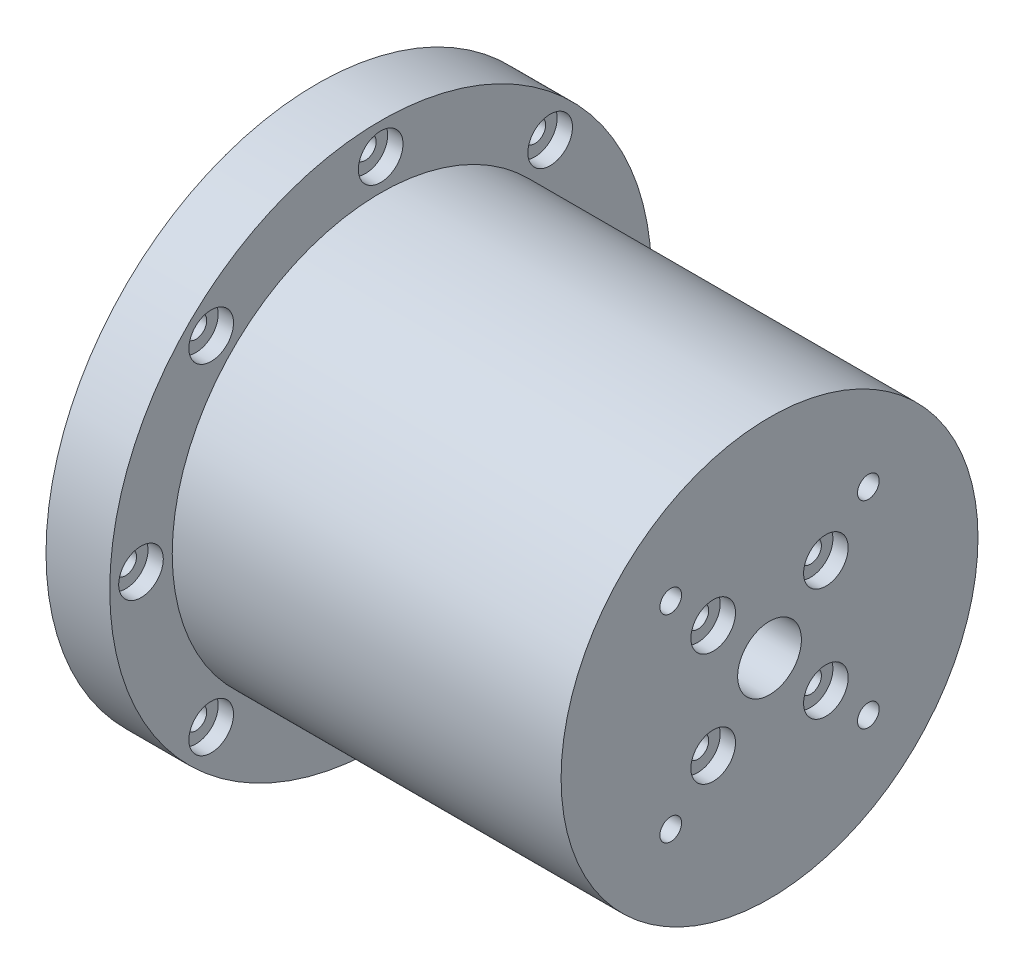
SolidWorks part; units mm, degrees
material "7075-O (SS)"
ref_plane "Front" through (0, 0, 0) normal (0, 0, 1) x (1, 0, 0)
ref_plane "Top" through (0, 0, 0) normal (0, 1, 0) x (1, 0, 0)
ref_plane "Right" through (0, 0, 0) normal (1, 0, 0) x (0, 0, -1)
sketch "Croquis1" plane through (0, 0, 0) normal (1, 0, 0) x (0, 0, -1)
  circle A0 centre (0, 0) radius 32.7
  circle A1 centre (0, 0) radius 5
  dimension "D1" = 65.4
  dimension "D2" = 10
extrude "Saliente-Extruir1" add sketch "Croquis1" along normal mid plane 8.5
hole_wizard "Refrentado para tornillo con cabeza troncocónica de M31" positions "Croquis2" profile "Croquis4" counterbore size "M3" standard "Ansi Metric" end condition up to next
sketch "Croquis2" plane through (4.25, 0, 0) normal (1, 0, 0) x (0, 0, -1)
  line L1 (-8.8388, -8.8388) -> (8.8388, -8.8388) construction
  line L2 (-8.8388, -8.8388) -> (-8.8388, 8.8388) construction
  line L3 (-8.8388, 8.8388) -> (8.8388, 8.8388) construction
  line L4 (8.8388, -8.8388) -> (8.8388, 8.8388) construction
  line L5 (-8.8388, -8.8388) -> (8.8388, 8.8388) construction
  line L6 (-8.8388, 8.8388) -> (8.8388, -8.8388) construction
  point P2 (8.8388, 8.8388)
  point P25 (-8.8388, -8.8388)
  point P26 (-8.8388, 8.8388)
  point P27 (8.8388, -8.8388)
  dimension "D1" = 25
sketch "Croquis4" plane through (4.25, 8.8388, -8.8388) normal (0, 1, 0) x (0, 0, -1)
  line L0 (0, 0) -> (0, 8.5)
  line L1 (0, 8.5) -> (1.7, 8.5)
  line L3 (1.7, 8.5) -> (1.7, 2.4)
  line L4 (1.7, 2.4) -> (3.5, 2.4)
  line L5 (3.5, 2.4) -> (3.5, 0)
  line L7 (3.5, 0) -> (0, 0)
  line L11 (0, -6.35) -> (0, 107.95) construction
  dimension "Diámetro de taladro hasta el siguiente" = 3.4
  dimension "Profundidad de taladro hasta el siguiente" = 8.5
  dimension "Diámetro de refrentado" = 7
  dimension "Profundidad de refrentado" = 2.4
sketch "Croquis5" plane through (-4.25, 0, 0) normal (-1, 0, 0) x (0, 0, 1)
  circle A0 centre (0, 0) radius 21.5
  circle A1 centre (0, 0) radius 32.7 construction
  circle A2 centre (0, 0) radius 32.7
  dimension "D1" = 43
extrude "Saliente-Extruir2" add sketch "Croquis5" along normal blind 55
hole_wizard "Taladro de margen para M31" positions "Croquis6" profile "Croquis8" hole size "M3" standard "Ansi Metric"
sketch "Croquis6" plane through (-59.25, 0, 0) normal (-1, 0, 0) x (0, 0, 1)
  line L1 (-17.075, -17.075) -> (17.075, -17.075) construction
  line L2 (-17.075, -17.075) -> (-17.075, 17.075) construction
  line L3 (-17.075, 17.075) -> (17.075, 17.075) construction
  line L4 (17.075, -17.075) -> (17.075, 17.075) construction
  line L5 (-17.075, -17.075) -> (17.075, 17.075) construction
  line L6 (-17.075, 17.075) -> (17.075, -17.075) construction
  point P2 (17.075, 17.075)
  point P25 (-17.075, -17.075)
  point P26 (-17.075, 17.075)
  point P27 (17.075, -17.075)
  dimension "D1" = 34.15
sketch "Croquis8" plane through (-59.25, 17.075, 17.075) normal (0, 1, 0) x (0, 0, 1)
  line L0 (0, 0) -> (0, 16.0215)
  line L1 (0, 16.0215) -> (1.7, 15)
  line L2 (1.7, 15) -> (1.7, 0)
  line L5 (1.7, 0) -> (0, 0)
  line L10 (0, 16.0215) -> (-1.7, 15) construction
  line L11 (0, -6.35) -> (0, 107.95) construction
  dimension "Diámetro de taladro" = 3.4
  dimension "Profundidad de taladro" = 15
  dimension "Ángulo de perforador" = 118
hole_wizard "Taladro de margen para M32" positions "Croquis9" profile "Croquis10" hole size "M3" standard "Ansi Metric"
sketch "Croquis9" plane through (4.25, 0, 0) normal (1, 0, 0) x (0, 0, -1)
  line L1 (-15.5, -15.5) -> (15.5, -15.5) construction
  line L2 (-15.5, -15.5) -> (-15.5, 15.5) construction
  line L3 (-15.5, 15.5) -> (15.5, 15.5) construction
  line L4 (15.5, -15.5) -> (15.5, 15.5) construction
  line L5 (-15.5, -15.5) -> (15.5, 15.5) construction
  line L6 (-15.5, 15.5) -> (15.5, -15.5) construction
  point P2 (15.5, 15.5)
  point P13 (-15.5, -15.5)
  point P14 (-15.5, 15.5)
  point P15 (15.5, -15.5)
  dimension "D1" = 31
sketch "Croquis10" plane through (4.25, 15.5, -15.5) normal (0, 1, 0) x (0, 0, -1)
  line L0 (0, 0) -> (0, 17.5215)
  line L1 (0, 17.5215) -> (1.7, 16.5)
  line L2 (1.7, 16.5) -> (1.7, 0)
  line L5 (1.7, 0) -> (0, 0)
  line L10 (0, 17.5215) -> (-1.7, 16.5) construction
  line L11 (0, -6.35) -> (0, 107.95) construction
  dimension "Diámetro de taladro" = 3.4
  dimension "Profundidad de taladro" = 16.5
  dimension "Ángulo de perforador" = 118
sketch "Croquis16" plane through (-59.25, 0, 0) normal (-1, 0, 0) x (0, 0, 1)
  line L1 (-21.5, -21.5) -> (21.5, -21.5) construction
  line L2 (-21.5, -21.5) -> (-21.5, 21.5) construction
  line L3 (-21.5, 21.5) -> (21.5, 21.5) construction
  line L4 (21.5, -21.5) -> (21.5, 21.5) construction
  line L5 (-21.5, -21.5) -> (21.5, 21.5) construction
  line L6 (-21.5, 21.5) -> (21.5, -21.5) construction
  line L15 (-16.5, 21.5) -> (16.5, 21.5)
  line L16 (-21.5, 16.5) -> (-21.5, -16.5)
  line L17 (-16.5, -21.5) -> (16.5, -21.5)
  line L18 (21.5, 16.5) -> (21.5, -16.5)
  circle A0 centre (0, 0) radius 21.5 construction
  circle A1 centre (0, 0) radius 32.7
  circle A2 centre (0, 0) radius 32.7
  arc A3 (-21.5, -16.5) -> (-16.5, -21.5) centre (-16.5, -16.5) ccw
  arc A4 (16.5, -21.5) -> (21.5, -16.5) centre (16.5, -16.5) ccw
  arc A5 (16.5, 21.5) -> (21.5, 16.5) centre (16.5, 16.5) cw
  arc A6 (-16.5, 21.5) -> (-21.5, 16.5) centre (-16.5, 16.5) ccw
  dimension "D2" = 5
  dimension "D1" = 0
extrude "Saliente-Extruir3" add sketch "Croquis16" along normal blind 7.5
sketch "Croquis17" plane through (-66.75, 0, 0) normal (-1, 0, 0) x (0, 0, 1)
  circle A0 centre (0, 0) radius 42.5
  circle A1 centre (0, 0) radius 32.7 construction
  circle A2 centre (0, 0) radius 32.7
  dimension "D1" = 85
extrude "Saliente-Extruir4" add sketch "Croquis17" against normal blind 10
hole_wizard "Refrentado para tornillo con cabeza troncocónica de M32" positions "Croquis18" profile "Croquis19" counterbore size "M3" standard "Ansi Metric" end condition up to next
sketch "Croquis18" plane through (-56.75, 0, 0) normal (1, 0, 0) x (0, 0, -1)
  line L0 (0, 39.05) -> (0, -39.05) construction
  line L1 (0, 42.5) -> (0, 32.7) construction
  circle A0 centre (0, 0) radius 42.5 construction
  circle A1 centre (0, 0) radius 32.7 construction
  point P0 (0, 37.6)
  point P15 (0, 37.6)
  point P20 (26.5872, 26.5872)
  point P21 (37.6, 0)
  point P22 (26.5872, -26.5872)
  point P23 (0, -37.6)
  point P24 (-26.5872, -26.5872)
  point P25 (-37.6, 0)
  point P26 (-26.5872, 26.5872)
  dimension "D1" = 8
sketch "Croquis19" plane through (-56.75, 37.6, 0) normal (0, 1, 0) x (0, 0, -1)
  line L0 (0, 0) -> (0, 10)
  line L1 (0, 10) -> (1.7, 10)
  line L3 (1.7, 10) -> (1.7, 2.4)
  line L4 (1.7, 2.4) -> (3.5, 2.4)
  line L5 (3.5, 2.4) -> (3.5, 0)
  line L7 (3.5, 0) -> (0, 0)
  line L11 (0, -6.35) -> (0, 107.95) construction
  dimension "Diámetro de taladro hasta el siguiente" = 3.4
  dimension "Profundidad de taladro hasta el siguiente" = 10
  dimension "Diámetro de refrentado" = 7
  dimension "Profundidad de refrentado" = 2.4
